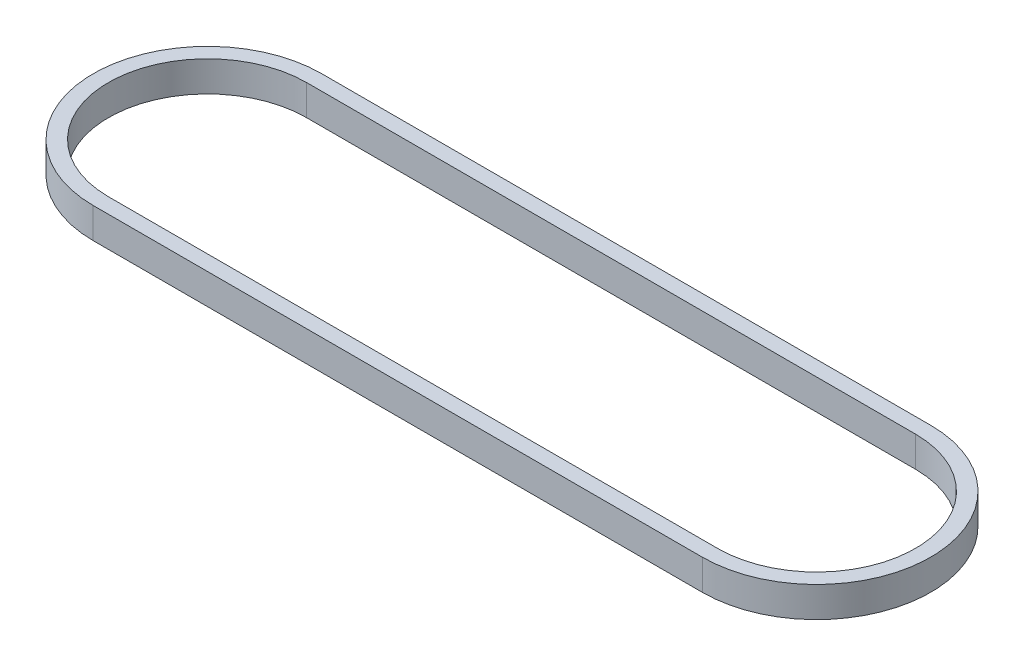
SolidWorks part; units mm, degrees
material "1023 Carbon Steel Sheet (SS)"
ref_plane "Front Plane" through (0, 0, 0) normal (0, 0, 1) x (1, 0, 0)
ref_plane "Top Plane" through (0, 0, 0) normal (0, 1, 0) x (1, 0, 0)
ref_plane "Right Plane" through (0, 0, 0) normal (1, 0, 0) x (0, 0, -1)
sketch "Sketch1" plane through (0, 0, 0) normal (0, 1, 0) x (1, 0, 0)
  line L0 (-40, 0) -> (40, 0) construction
  line L1 (-40, 13) -> (40, 13)
  line L2 (-40, -13) -> (40, -13)
  line L3 (-40, 15) -> (40, 15)
  line L4 (-40, -15) -> (40, -15)
  arc A0 (-40, 13) -> (-40, -13) centre (-40, 0) ccw
  arc A1 (40, -13) -> (40, 13) centre (40, 0) ccw
  arc A2 (40, -15) -> (40, 15) centre (40, 0) ccw
  arc A3 (-40, 15) -> (-40, -15) centre (-40, 0) ccw
  point P3 (0, 0)
  dimension "D3" = 13
  dimension "D2" = 80
  dimension "D1" = 2
extrude "Boss-Extrude1" add sketch "Sketch1" along normal blind 4
